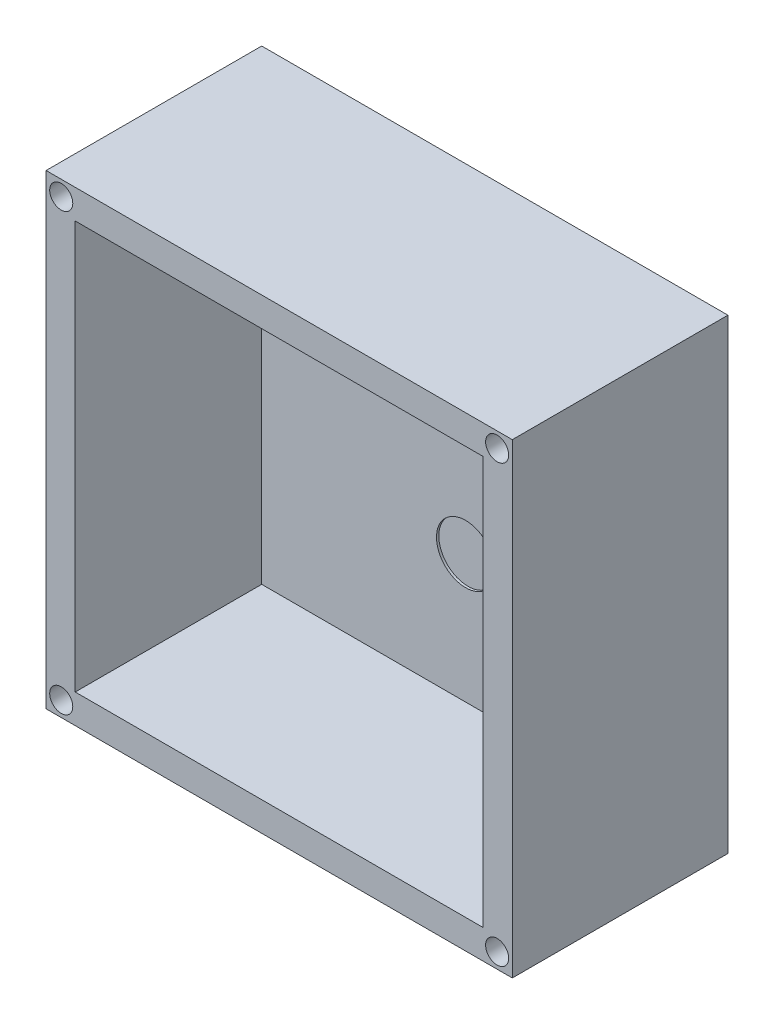
SolidWorks part; units mm, degrees
ref_plane "Front Plane" through (0, 0, 0) normal (0, 0, 1) x (1, 0, 0)
ref_plane "Top Plane" through (0, 0, 0) normal (0, 1, 0) x (1, 0, 0)
ref_plane "Right Plane" through (0, 0, 0) normal (1, 0, 0) x (0, 0, -1)
sketch "Sketch1" plane through (0, 0, 0) normal (0, 0, 1) x (1, 0, 0)
  line L1 (0, 0) -> (50.8, 0)
  line L2 (0, 0) -> (0, 50.8)
  line L3 (0, 50.8) -> (50.8, 50.8)
  line L4 (50.8, 0) -> (50.8, 50.8)
  dimension "D1" = 50.8
  dimension "D2" = 50.8
extrude "Boss-Extrude1" add sketch "Sketch1" along normal blind 3.175
sketch "Sketch3" plane through (0, 0, 3.175) normal (0, 0, 1) x (1, 0, 0)
  line L1 (0, 50.8) -> (50.8, 50.8)
  line L2 (0, 50.8) -> (0, 0)
  line L3 (0, 0) -> (50.8, 0)
  line L4 (50.8, 50.8) -> (50.8, 0)
  line L5 (3.175, 47.625) -> (47.6123, 47.625)
  line L6 (3.175, 47.625) -> (3.175, 3.175)
  line L7 (3.175, 3.175) -> (47.6123, 3.175)
  line L8 (47.6123, 47.625) -> (47.6123, 3.175)
  dimension "D1" = 3.175
  dimension "D2" = 3.175
  dimension "D3" = 3.1877
  dimension "D4" = 3.175
extrude "Boss-Extrude2" add sketch "Sketch3" along normal blind 20.32
sketch "Sketch4" plane through (0, 0, 3.175) normal (0, 0, 1) x (1, 0, 0)
  line L0 (25.3936, 3.175) -> (25.3937, 47.625) construction
  line L1 (3.175, 3.175) -> (47.6123, 3.175) construction
  line L2 (47.6123, 47.625) -> (3.175, 47.625) construction
  line L3 (3.175, 3.175) -> (47.6123, 3.175) construction
  circle A0 centre (25.3936, 17.145) radius 12.7
  circle A1 centre (25.3937, 35.1409) radius 5.2959
  circle A2 centre (25.3936, 17.145) radius 3.175
  circle A3 centre (25.3937, 35.1409) radius 3.175
  dimension "D2" = 25.4
  dimension "D4" = 10.5918
  dimension "D5" = 6.35
  dimension "D6" = 6.35
  dimension "D1" = 13.97
  dimension "D3" = 17.9959
extrude "Cut-Extrude1" cut sketch "Sketch4" against normal blind 0.254 contours A2
sketch "Sketch6" plane through (0, 0, 23.495) normal (0, 0, 1) x (1, 0, 0)
  line L8 (1.651, 49.149) -> (1.651, 1.651)
  line L9 (1.651, 1.651) -> (49.149, 1.651)
  line L10 (49.149, 1.651) -> (49.149, 49.149)
  line L11 (49.149, 49.149) -> (1.651, 49.149)
  line L12 (1.651, 49.149) -> (1.651, 1.651)
  line L13 (1.651, 1.651) -> (49.149, 1.651)
  line L14 (49.149, 1.651) -> (49.149, 49.149)
  line L15 (49.149, 49.149) -> (1.651, 49.149)
  circle A0 centre (1.651, 49.149) radius 1.2573
  circle A1 centre (49.149, 49.149) radius 1.2573
  circle A2 centre (49.149, 1.651) radius 1.2573
  circle A3 centre (1.651, 1.651) radius 1.2573
  dimension "D2" = 2.5146
  dimension "D1" = 1.651
extrude "Cut-Extrude2" cut sketch "Sketch6" against normal blind 9.525 contours A0 | A1 | A2 | A3
extrude "Cut-Extrude3" cut sketch "Sketch4<3>" against normal through all contours A3
sketch "Sketch4<3>" plane through (0, 0, 3.175) normal (0, 0, 1) x (1, 0, 0) same geometry as "Sketch4"
equation "\"Alpha\"= 20"
equation "\"RPMout\"= 1100"
equation "\"T1\"= 18"
equation "\"T2\"= 48"
equation "\"GR\"= \"T1\" / \"T2\""
equation "\"RPMIn\"= \"RPMout\" / \"GR\""
equation "\"DI\"= .125"
equation "\"Li\"= 1"
equation "\"D2\"= .25"
equation "\"l2\"= 1"
